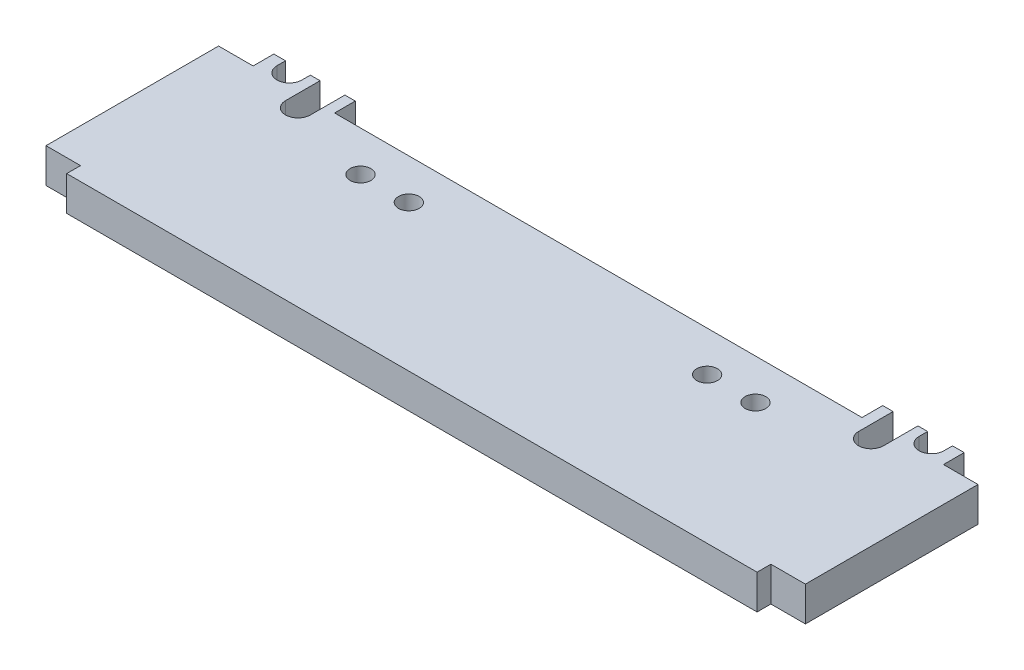
SolidWorks part; units mm, degrees
ref_plane "Front Plane" through (0, 0, 0) normal (0, 0, 1) x (1, 0, 0)
ref_plane "Top Plane" through (0, 0, 0) normal (0, 1, 0) x (1, 0, 0)
ref_plane "Right Plane" through (0, 0, 0) normal (1, 0, 0) x (0, 0, -1)
sketch "Sketch1" plane through (0, 0, 0) normal (1, 0, 0) x (0, 0, -1)
  line L1 (-17.1369, 5.602) -> (9.8631, 5.602)
  line L2 (-17.1369, 5.602) -> (-17.1369, 0.602)
  line L3 (-17.1369, 0.602) -> (9.8631, 0.602)
  line L4 (9.8631, 5.602) -> (9.8631, 0.602)
  dimension "D1" = 27
  dimension "D2" = 5
extrude "Boss-Extrude1" add sketch "Sketch1" along normal blind 110
sketch "Sketch2" plane through (0, 0.602, 0) normal (0, -1, 0) x (1, 0, 0)
  line L1 (0, -9.8631) -> (5, -9.8631)
  line L2 (0, -9.8631) -> (0, -7.3631)
  line L3 (0, -7.3631) -> (5, -7.3631)
  line L4 (5, -9.8631) -> (5, -7.3631)
  dimension "D1" = 5
  dimension "D2" = 2.5
sketch "Sketch5" plane through (0, 0, 0) normal (-1, 0, 0) x (0, 0, 1)
  line L0 (0, 0.602) -> (0, 5.602) construction
  line L1 (17.1369, 0.602) -> (-9.8631, 0.602) construction
  line L2 (-9.8631, 5.602) -> (17.1369, 5.602) construction
sketch "Sketch6" plane through (0, 5.602, 0) normal (0, 1, 0) x (1, 0, 0)
  line L1 (0, -17.1369) -> (5, -17.1369)
  line L2 (0, -17.1369) -> (0, -15.1369)
  line L3 (0, -15.1369) -> (5, -15.1369)
  line L4 (5, -17.1369) -> (5, -15.1369)
  dimension "D1" = 5
  dimension "D2" = 2
sketch "Sketch7" plane through (0, 5.602, 0) normal (0, 1, 0) x (1, 0, 0)
  line L0 (110, -3.6369) -> (0, 0) construction
  line L1 (110, 9.8631) -> (110, -17.1369) construction
  line L2 (55, -1.8184) -> (55, -17.1369) construction
  line L3 (110, -17.1369) -> (0, -17.1369) construction
sketch "Sketch8" plane through (0, 0, 17.1369) normal (0, 0, 1) x (1, 0, 0)
  line L0 (55, 5.602) -> (55, 0.602) construction
  line L1 (110, 0.602) -> (0, 0.602) construction
ref_plane "Plane3" through (55, 0, 0) normal (1, 0, 0) x (0, 0, -1)
sketch "Sketch13" plane through (0, 5.602, 0) normal (0, 1, 0) x (1, 0, 0)
  line L0 (55, -1.8184) -> (4.7941, -1.8184) construction
  line L1 (29.897, -1.8184) -> (29.897, 9.8631) construction
  line L2 (110, 9.8631) -> (0, 9.8631) construction
  line L3 (29.897, 4.0223) -> (26.397, 4.0223) construction
  line L4 (17.3455, 4.0223) -> (17.3455, 9.8631) construction
  line L5 (29.897, 4.0223) -> (33.397, 4.0223) construction
  dimension "D1" = 3.5
  dimension "D2" = 3.5
hole_wizard "M3 Tapped Hole1" positions "3DSketch2" profile "Sketch14" tap size "M3" standard "ISO"
sketch3d "3DSketch2"
  point P0 (26.397, 5.602, -4.0223)
  point P3 (33.397, 5.602, -4.0223)
sketch "Sketch14" plane through (26.397, 5.602, -4.0223) normal (1, 0, 0) x (0, 0, 1)
  line L0 (0, 0) -> (0, 8.2511)
  line L1 (0, 8.2511) -> (1.25, 7.5)
  line L2 (1.25, 7.5) -> (1.25, 6)
  line L3 (1.25, 6) -> (1.5, 6)
  line L4 (1.5, 6) -> (1.5, 0)
  line L5 (1.5, 0) -> (0, 0)
  line L10 (0, 8.2511) -> (-1.25, 7.5) construction
  line L11 (0, -6.35) -> (0, 107.95) construction
  dimension "Tap Drill Dia." = 2.5
  dimension "Tap Drill Depth" = 7.5
  dimension "Thread Major Dia." = 3
  dimension "Thread Depth" = 6
  dimension "Drill Angle" = 118
ref_plane "Plane4" through (55, 0, 0) normal (1, 0, 0) x (0, 0, -1)
mirror "Mirror3" about plane through (55, 0, 0) normal (1, 0, 0) of "M3 Tapped Hole1"
extrude "Cut-Extrude1" cut sketch "Sketch6" against normal blind 10 contours L4 L3 L2 L1
mirror "Mirror4" about plane through (55, 0, 0) normal (1, 0, 0) of "Cut-Extrude1"
sketch "Sketch17" plane through (0, 5.602, 0) normal (0, 1, 0) x (1, 0, 0)
  line L0 (110, 9.8631) -> (105, 9.8631) construction
  line L1 (110, 9.8631) -> (0, 9.8631) construction
  line L2 (105, 9.8631) -> (105, 12.8631)
  line L3 (103.25, 12.8631) -> (99.674, 12.8631)
  line L4 (105, 12.8631) -> (103.25, 12.8631)
  line L5 (105, 9.8631) -> (97.924, 9.8631)
  line L6 (99.674, 12.8631) -> (93.2002, 12.8631)
  line L13 (93.2002, 12.8631) -> (93.2002, 9.8631)
  line L14 (93.2002, 9.8631) -> (97.924, 9.8631)
  dimension "D4" = 3
  dimension "D1" = 5
  dimension "D2" = 3
  dimension "D3" = 1.75
extrude "Boss-Extrude2" add sketch "Sketch17" against normal blind 5
sketch "Sketch18" plane through (0, 5.602, 0) normal (0, 1, 0) x (1, 0, 0)
  line L0 (55, -17.1369) -> (55, 9.8631) construction
  line L1 (93.2002, 9.8631) -> (0, 9.8631) construction
sketch "Sketch19" plane through (0, 0, -9.8631) normal (0, 0, -1) x (-1, 0, 0)
  line L0 (-55, 5.602) -> (-55, 0.602) construction
  line L1 (-93.2002, 0.602) -> (0, 0.602) construction
ref_plane "Plane5" through (55, 0, 0) normal (-1, 0, 0) x (0, 0, 1)
mirror "Mirror5" about plane through (55, 0, 0) normal (-1, 0, 0) of "Boss-Extrude2"
sketch "Sketch20" plane through (0, 5.602, 0) normal (0, 1, 0) x (1, 0, 0)
  line L0 (97.924, 9.8631) -> (97.924, 5.623) construction
sketch "Sketch21" plane through (0, 5.602, 0) normal (0, 1, 0) x (1, 0, 0)
  line L0 (96.5031, 12.8631) -> (98.3031, 12.8631)
  line L1 (105, 12.8631) -> (93.2002, 12.8631) construction
  line L2 (96.5031, 12.8631) -> (94.7026, 12.8631)
  line L3 (96.5031, 12.8631) -> (96.5031, 9.2179) construction
  line L4 (98.3031, 12.8631) -> (98.3031, 7.8631)
  line L5 (94.7026, 12.8631) -> (94.7026, 7.8631)
  arc A0 (98.3031, 7.8631) -> (94.7026, 7.8631) centre (96.5028, 7.8631) cw
  dimension "D1" = 5
  dimension "D2" = 1.8
extrude "Cut-Extrude2" cut sketch "Sketch21" against normal blind 10
sketch "Sketch22" plane through (0, 5.602, 0) normal (0, 1, 0) x (1, 0, 0)
  line L0 (101.5051, 12.8631) -> (101.5051, 11.6291) construction
  line L1 (105, 12.8631) -> (98.3031, 12.8631) construction
  line L2 (101.5051, 12.8631) -> (103.3051, 12.8631)
  line L3 (103.3051, 12.8631) -> (103.3051, 11.6291)
  line L4 (101.5051, 12.8631) -> (99.7051, 12.8631)
  line L5 (99.7051, 12.8631) -> (99.7051, 11.6291)
  arc A0 (103.3051, 11.6291) -> (99.7051, 11.6291) centre (101.5051, 11.6291) cw
  dimension "D1" = 1.8
  dimension "D2" = 1.8
extrude "Cut-Extrude3" cut sketch "Sketch22" against normal blind 10 contours A0 L5 L4 L2 L3
ref_plane "Plane6" through (55, 0, 0) normal (-1, 0, 0) x (0, 0, 1)
mirror "Mirror6" about plane through (55, 0, 0) normal (-1, 0, 0) of "Cut-Extrude3", "Cut-Extrude2"
